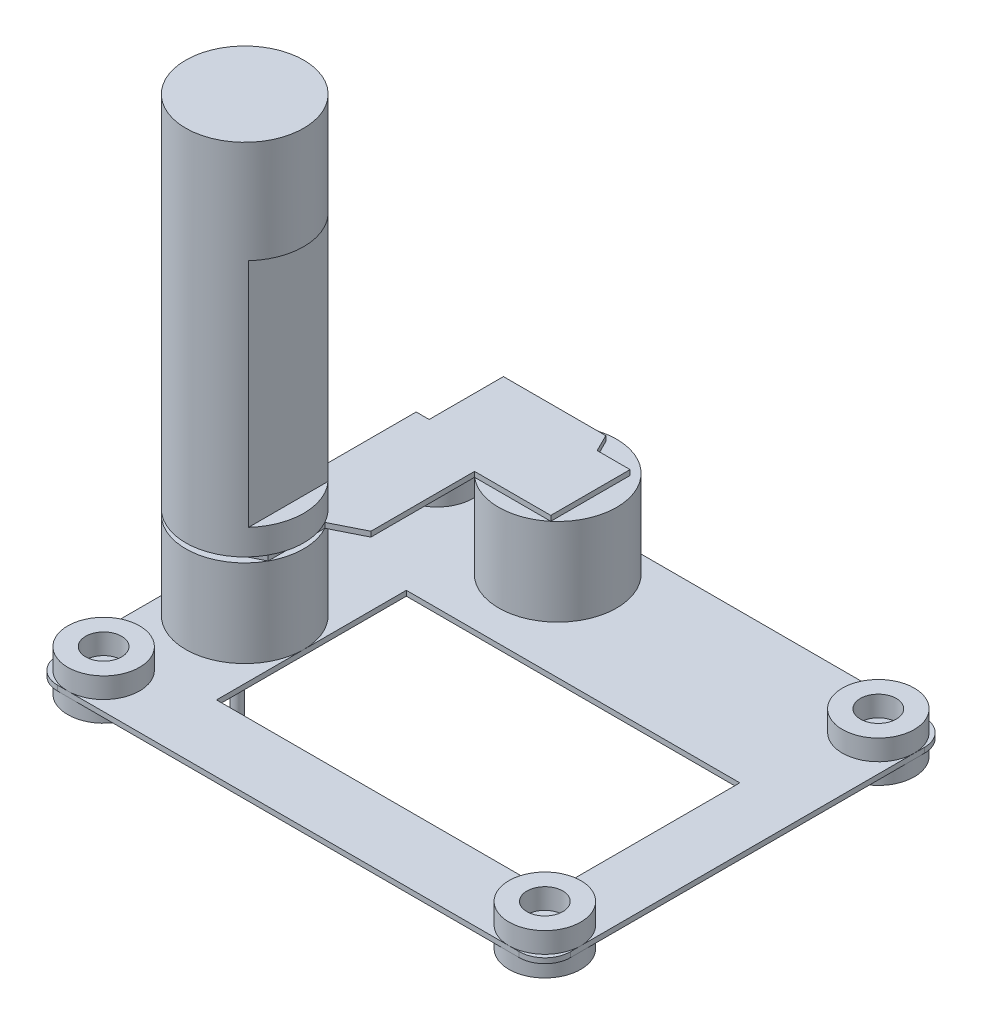
SolidWorks part; units mm, degrees
ref_plane "Plan de face" through (0, 0, 0) normal (0, 0, 1) x (1, 0, 0)
ref_plane "Plan de dessus" through (0, 0, 0) normal (0, 1, 0) x (1, 0, 0)
ref_plane "Plan de droite" through (0, 0, 0) normal (1, 0, 0) x (0, 0, -1)
sketch "Esquisse4" plane through (0, 0, 0) normal (0, 1, 0) x (1, 0, 0)
  line L1 (-50, -39.5) -> (50, -39.5)
  line L2 (-50, -39.5) -> (-50, 39.5)
  line L3 (-50, 39.5) -> (50, 39.5)
  line L4 (50, -39.5) -> (50, 39.5)
  line L5 (-50, -39.5) -> (50, 39.5) construction
  line L6 (-50, 39.5) -> (50, -39.5) construction
  point P0 (0, 0)
  dimension "D1" = 100
  dimension "D2" = 79
extrude "Boss.-Extru.3" add sketch "Esquisse4" against normal blind 1
sketch "Esquisse1" plane through (0, 0, 0) normal (0, 1, 0) x (1, 0, 0)
  line L0 (36, 39.5) -> (36, 25.5) construction
  line L1 (-50, -39.5) -> (50, -39.5)
  line L2 (-50, -39.5) -> (-50, 39.5)
  line L3 (-50, 39.5) -> (50, 39.5)
  line L4 (50, -39.5) -> (50, 39.5)
  line L5 (-50, -39.5) -> (50, 39.5) construction
  line L6 (-50, 39.5) -> (50, -39.5) construction
  line L7 (36, 25.5) -> (50, 25.5) construction
  line L8 (36, 25.5) -> (50, 39.5) construction
  line L9 (-36, 39.5) -> (-36, 25.5) construction
  line L10 (-36, 25.5) -> (-50, 25.5) construction
  line L11 (-36, 25.5) -> (-50, 39.5) construction
  line L12 (-50, -25.5) -> (-36, -25.5) construction
  line L13 (-36, -25.5) -> (-36, -39.5) construction
  line L14 (-36, -25.5) -> (-50, -39.5) construction
  line L15 (50, -25.5) -> (36, -25.5) construction
  line L16 (36, -25.5) -> (36, -39.5) construction
  line L17 (36, -25.5) -> (50, -39.5) construction
  circle A0 centre (43, 32.5) radius 7
  circle A1 centre (-43, 32.5) radius 7
  circle A2 centre (-43, -32.5) radius 7
  circle A3 centre (43, -32.5) radius 7
  circle A4 centre (-43, 32.5) radius 3.5
  circle A5 centre (43, 32.5) radius 3.5
  circle A6 centre (43, -32.5) radius 3.5
  circle A7 centre (-43, -32.5) radius 3.5
  point P0 (0, 0)
  dimension "D4" = 14
  dimension "D5" = 14
  dimension "D12" = 7
  dimension "D13" = 7
  dimension "D14" = 7
  dimension "D15" = 7
  dimension "D1" = 100
  dimension "D2" = 79
  dimension "D3" = 14
  dimension "D6" = 14
  dimension "D7" = 14
  dimension "D8" = 14
  dimension "D9" = 14
  dimension "D10" = 14
  dimension "D11" = 14
extrude "Boss.-Extru.4" add sketch "Esquisse1" against normal blind 4 and the other way blind 4 contours A0 | A1 | A2 | A3 region at (-47.8097, 0, 37.3097) region at (38.1903, 0, 27.6903) region at (-47.8097, 0, -37.3097) region at (38.1903, 0, -27.6903)
sketch "Esquisse6" plane through (0, 0, 0) normal (0, 1, 0) x (1, 0, 0)
  line L0 (-38.5, -9.5) -> (-50, -9.5) construction
  line L1 (-50, 32.5) -> (-50, -32.5) construction
  line L2 (-38.5, -9.5) -> (-38.5, -39.5) construction
  line L3 (-43, -39.5) -> (43, -39.5) construction
  line L4 (-15, 28) -> (-15, 39.5) construction
  line L5 (43, 39.5) -> (-43, 39.5) construction
  line L6 (-15, 28) -> (-50, 28) construction
  circle A0 centre (-38.5, -9.5) radius 11.5
  circle A1 centre (-15, 28) radius 11.5
  dimension "D1" = 23
  dimension "D2" = 23
  dimension "D3" = 11.5
  dimension "D4" = 30
  dimension "D5" = 11.5
  dimension "D6" = 35
extrude "Boss.-Extru.5" add sketch "Esquisse6" along normal blind 17
sketch "Esquisse7" plane through (0, 17, 0) normal (0, 1, 0) x (1, 0, 0)
  line L0 (-38.1438, -19.8875) -> (-28.4142, -15.0251)
  line L1 (-28.4142, -15.0251) -> (-28.4142, -3.9749)
  line L2 (-28.4142, -3.9749) -> (-22.4283, -0.9834)
  line L3 (-22.4283, -0.9834) -> (-22.4283, 19.221)
  line L4 (-22.4283, 19.221) -> (-7.5717, 19.221)
  line L5 (-7.5717, 19.221) -> (-7.5717, 34.6801)
  line L6 (-7.5717, 34.6801) -> (-13.9887, 34.6801)
  line L7 (-13.9887, 34.6801) -> (-15.6674, 38.0391)
  line L8 (-15.6674, 38.0391) -> (-35.6132, 38.0391)
  line L9 (-35.6132, 38.0391) -> (-35.6132, 23.5595)
  line L12 (-38.1438, 23.5595) -> (-38.1438, 0)
  line L13 (-38.1438, 0) -> (-38.1438, -19.8875)
  line L14 (-38.1438, 23.5595) -> (-35.6132, 23.5595)
  circle A0 centre (-38.5, -9.5) radius 11.5 construction
  circle A1 centre (-38.5, -9.5) radius 11.5 construction
  circle A2 centre (-15, 28) radius 11.5 construction
  circle A3 centre (-15, 28) radius 11.5 construction
extrude "Boss.-Extru.6" add sketch "Esquisse7" along normal blind 1
sketch "Esquisse8" plane through (0, 0, 0) normal (0, 1, 0) x (1, 0, 0)
  line L0 (-43, -39.5) -> (43, -39.5) construction
  line L1 (-27, -26.5) -> (38, -26.5)
  line L2 (-27, -26.5) -> (-27, 10.5)
  line L3 (-27, 10.5) -> (38, 10.5)
  line L4 (38, -26.5) -> (38, 10.5)
  line L5 (50, -32.5) -> (50, 32.5) construction
  dimension "D1" = 13
  dimension "D2" = 37
  dimension "D3" = 65
  dimension "D4" = 12
extrude "Enlèv. mat.-Extru.1" cut sketch "Esquisse8" against normal blind 1
sketch "Esquisse9" plane through (0, -1, 0) normal (0, -1, 0) x (1, 0, 0)
  line L1 (-50, -32.5) -> (-50, 32.5) construction
  line L4 (-43, 39.5) -> (43, 39.5) construction
  circle A0 centre (-40, 9.5) radius 1
  dimension "D1" = 2
  dimension "D2" = 30
  dimension "D3" = 10
extrude "Boss.-Extru.7" add sketch "Esquisse9" along normal blind 18
sketch "Esquisse10" plane through (0, 18, 0) normal (0, 1, 0) x (1, 0, 0)
  line L0 (-38.5, 2) -> (-38.5, -21) construction
  arc A1 (-27, -9.5) -> (-50, -9.5) centre (-38.5, -9.5) ccw construction
  arc A2 (-50, -9.5) -> (-27, -9.5) centre (-38.5, -9.5) ccw construction
  circle A3 centre (-38.5, -9.5) radius 11.5
extrude "Boss.-Extru.8" add sketch "Esquisse10" along normal blind 50
fillet "Congé2" radius 5 4 edges at (-50, -0.5, 39.5) (50, -0.5, 39.5) (50, -0.5, -39.5) (-50, -0.5, -39.5)
sketch "Esquisse11" plane through (0, 68, 0) normal (0, 1, 0) x (1, 0, 0)
  line L0 (-27, -9.5) -> (-30, -9.5) construction
  line L1 (-30, -17.246) -> (-30, -1.754)
  circle A0 centre (-38.5, -9.5) radius 11.5 construction
  arc A1 (-30, -1.754) -> (-30, -17.246) centre (-38.5, -9.5) cw
  point P9 (-30, -9.5)
  dimension "D1" = 3
extrude "Enlèv. mat.-Extru.3" cut sketch "Esquisse11" against normal blind 45
sketch "Esquisse12" plane through (0, 68, 0) normal (0, 1, 0) x (1, 0, 0)
  circle A0 centre (-38.5, -9.5) radius 11.5
extrude "Boss.-Extru.9" add sketch "Esquisse12" along normal blind 20
